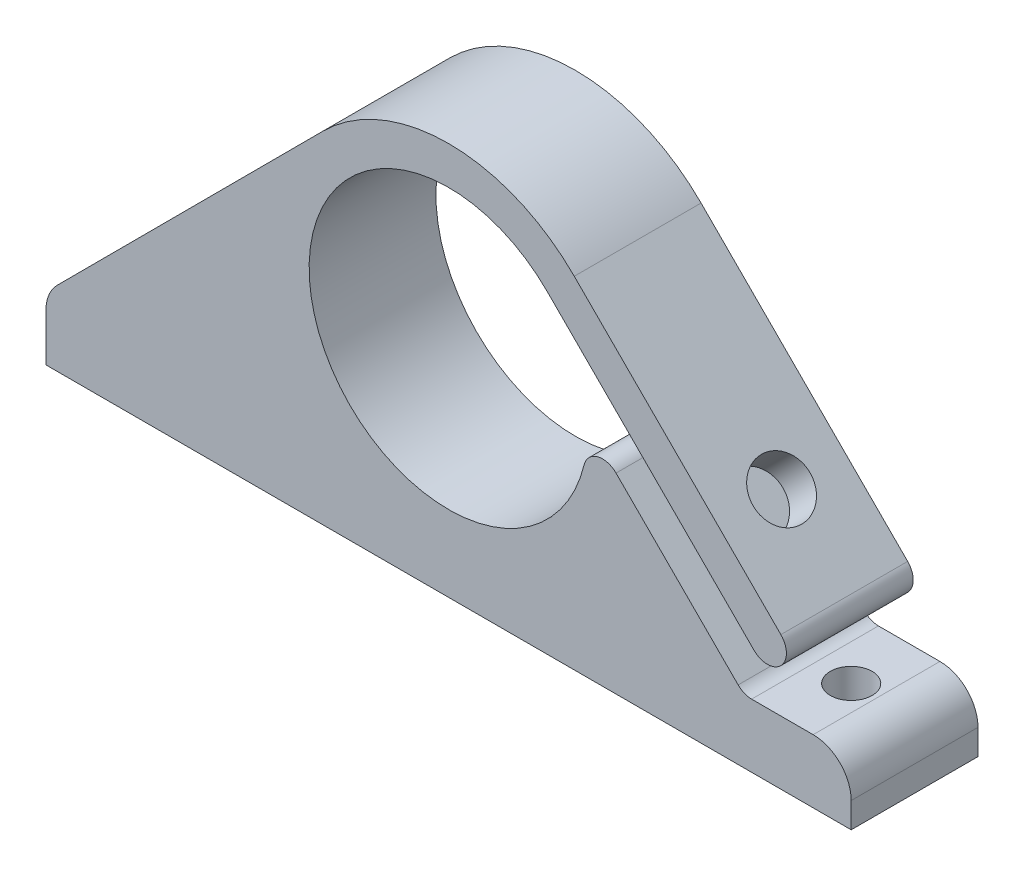
SolidWorks part; units mm, degrees
material "Сплав 2024"
ref_plane "Спереди" through (0, 0, 0) normal (0, 0, 1) x (1, 0, 0)
ref_plane "Сверху" through (0, 0, 0) normal (0, 1, 0) x (1, 0, 0)
ref_plane "Справа" through (0, 0, 0) normal (1, 0, 0) x (0, 0, -1)
sketch "Эскиз1" plane through (0, 0, 0) normal (0, 0, 1) x (1, 0, 0)
  line L0 (0, 32.0117) -> (0, -47.9255) construction
  line L1 (-31.75, -12) -> (-9.9106, 9.8884)
  line L3 (-31.75, -12) -> (-31.75, -17)
  line L4 (-31.75, -17) -> (31.75, -17)
  line L5 (31.75, -12) -> (31.75, -17)
  line L6 (-31.75, -12) -> (31.75, -17) construction
  line L7 (-31.75, -17) -> (31.75, -12) construction
  line L8 (31.75, -12) -> (9.9106, 9.8884)
  circle A0 centre (0, 0) radius 11
  arc A1 (9.9106, 9.8884) -> (-9.9106, 9.8884) centre (0, 0) ccw
  circle A3 centre (0, 0) radius 14 construction
  point P5 (0, -14.5)
  point P12 (14, 0)
  dimension "D1" = 22
  dimension "D5" = 14.5
  dimension "D3" = 5
  dimension "D4" = 63.5
  dimension "D6" = 5
  dimension "D2" = 3
extrude "Бобышка-Вытянуть1" add sketch "Эскиз1" along normal blind 10
sketch "Эскиз2" plane through (0, 0, 10) normal (0, 0, 1) x (1, 0, 0)
  line L1 (7.7869, 7.7695) -> (24.5188, -9)
  line L2 (7.7869, 7.7695) -> (10.9957, 0.306)
  line L3 (10.9957, 0.306) -> (23.2742, -12)
  line L6 (31.75, -12) -> (9.9106, 9.8884) construction
  line L7 (31.75, -12) -> (-31.75, -12) construction
  line L9 (31.75, -12) -> (23.2742, -12)
  line L10 (31.75, -12) -> (31.75, -9)
  line L11 (31.75, -9) -> (24.5188, -9)
  circle A0 centre (0, 0) radius 11 construction
  dimension "D1" = 3
  dimension "D2" = 3
  dimension "D3" = 3
extrude "Вырез-Вытянуть1" cut sketch "Эскиз2" against normal through all
fillet "Скругление1" radius 1.5 4 edges at (23.2742, -12, 5) (24.5188, -9, 5) (28.7567, -9, 5) (10.9957, 0.306, 5)
sketch "Эскиз3" plane through (0, -17, 0) normal (0, -1, 0) x (1, 0, 0)
  line L0 (-31.75, 5) -> (31.75, 5) construction
  line L1 (-31.75, 10) -> (-31.75, 0) construction
  line L2 (31.75, 10) -> (31.75, 0) construction
  line L3 (-26.75, 10) -> (-26.75, 0) construction
  line L4 (-31.75, 10) -> (31.75, 10) construction
  line L5 (-31.75, 0) -> (31.75, 0) construction
  line L6 (26.75, 10) -> (26.75, 0) construction
  dimension "D1" = 5
  dimension "D2" = 5
hole_wizard "Отверстие обработанное метчиком M4x0.71" positions "Эскиз5" profile "Эскиз4" tap size "M4x0.7" standard "Ansi Metric"
sketch "Эскиз5" plane through (0, -17, 0) normal (0, -1, 0) x (-1, 0, 0)
  line L0 (31.75, -5) -> (-31.75, -5) construction
  line L1 (26.75, -10) -> (26.75, 0) construction
  line L2 (-26.75, -10) -> (-26.75, 0) construction
  point P0 (26.75, -5)
  point P2 (-26.75, -5)
sketch "Эскиз4" plane through (-26.75, -17, 5) normal (1, 0, 0) x (0, 0, -1)
  line L0 (0, 0) -> (0, 5.9914)
  line L1 (0, 5.9914) -> (1.65, 5)
  line L2 (1.65, 5) -> (1.65, 0)
  line L5 (1.65, 0) -> (0, 0)
  line L10 (0, 5.9914) -> (-1.65, 5) construction
  line L11 (0, -6.35) -> (0, 107.95) construction
  dimension "Диаметр сверла" = 3.3
  dimension "Глубина сверла" = 5
  dimension "Угол заточки сверла" = 118
cosmetic thread "Отверстие резьбы1" parameters "D1"=5, "D2"=4
cosmetic thread "Отверстие резьбы2" parameters "D1"=5, "D2"=4
sketch "Эскиз6" plane through (9.9106, 9.8884, 0) normal (0.7079, 0.7063, 0) x (0, 0, -1)
  line L0 (-5, -23.0668) -> (-5, 0) construction
  line L1 (-10, -23.0668) -> (0, -23.0668) construction
  line L2 (-10, 0) -> (0, 0) construction
  line L3 (-10, -16.0668) -> (0, -16.0668) construction
  line L4 (-10, -23.0668) -> (-10, 0) construction
  line L5 (0, -23.0668) -> (0, 0) construction
  dimension "D1" = 7
hole_wizard "Отверстие с зазором M41" positions "Эскиз8" profile "Эскиз7" hole size "M4" standard "Ansi Metric" end condition up to next
sketch "Эскиз8" plane through (9.9106, 9.8884, 0) normal (0.7079, 0.7063, 0) x (0, 0, -1)
  line L0 (-5, -23.0668) -> (-5, 0) construction
  line L1 (-10, -16.0668) -> (0, -16.0668) construction
  point P0 (-5, -16.0668)
sketch "Эскиз7" plane through (21.2588, -1.4852, 5) normal (0, 0, 1) x (-0.7063, 0.7079, 0)
  line L0 (0, 0) -> (0, 3)
  line L1 (0, 3) -> (2.25, 3)
  line L2 (2.25, 3) -> (2.25, 0)
  line L5 (2.25, 0) -> (0, 0)
  line L11 (0, -6.35) -> (0, 107.95) construction
  dimension "Диаметр сквозного отверстия" = 4.5
  dimension "Глубина сквозного отверстия" = 3
hole_wizard "Отверстие обработанное метчиком M4x0.72" positions "Эскиз10" profile "Эскиз9" tap size "M4x0.7" standard "Ansi Metric"
sketch "Эскиз10" plane through (5.6632, 5.6505, 0) normal (0.7079, 0.7063, 0) x (0, 0, -1)
  line L0 (-5, -23.0668) -> (-5, 0) construction
  line L1 (-10, -16.0668) -> (0, -16.0668) construction
  point P0 (-5, -16.0668)
sketch "Эскиз9" plane through (17.0114, -5.7231, 5) normal (0, 0, 1) x (-0.7063, 0.7079, 0)
  line L0 (0, 0) -> (0, 10.9914)
  line L1 (0, 10.9914) -> (1.65, 10)
  line L2 (1.65, 10) -> (1.65, 0)
  line L5 (1.65, 0) -> (0, 0)
  line L10 (0, 10.9914) -> (-1.65, 10) construction
  line L11 (0, -6.35) -> (0, 107.95) construction
  dimension "Диаметр сверла" = 3.3
  dimension "Глубина сверла" = 10
  dimension "Угол заточки сверла" = 118
cosmetic thread "Отверстие резьбы3" parameters "D1"=8, "D2"=4
fillet "Скругление2" radius 3 2 edges at (-31.75, -12, 5) (31.75, -12, 5)
